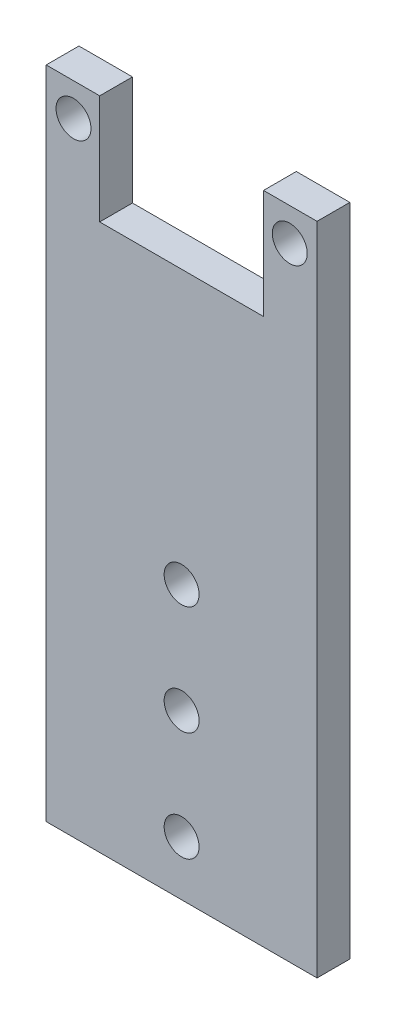
SolidWorks part; units mm, degrees
ref_plane "Front Plane" through (0, 0, 0) normal (0, 0, 1) x (1, 0, 0)
ref_plane "Top Plane" through (0, 0, 0) normal (0, 1, 0) x (1, 0, 0)
ref_plane "Right Plane" through (0, 0, 0) normal (1, 0, 0) x (0, 0, -1)
sketch "Sketch1" plane through (0, 0, 0) normal (0, 0, 1) x (1, 0, 0)
  line L0 (-7.5, 10) -> (-7.5, 0)
  line L1 (-7.5, 0) -> (7.5, 0)
  line L2 (7.5, 0) -> (7.5, 10)
  line L3 (7.5, 10) -> (12.4, 10)
  line L4 (12.4, 10) -> (12.4, -50)
  line L5 (12.4, -50) -> (-12.4, -50)
  line L6 (-12.4, -50) -> (-12.4, 10)
  line L7 (-12.4, 10) -> (-7.5, 10)
  line L8 (-9.9, 7) -> (9.9, 7) construction
  circle A0 centre (-9.9, 7) radius 1.6
  circle A1 centre (9.9, 7) radius 1.6
  circle A2 centre (0, -25) radius 1.6
  circle A3 centre (0, -35) radius 1.6
  circle A4 centre (0, -45) radius 1.6
  point P18 (0, 0)
  point P19 (0, 7)
  point P20 (0, 0)
  point P22 (0, -25)
  dimension "D1" = 3.2
  dimension "D2" = 10
  dimension "D3" = 10
  dimension "D4" = 19.8
  dimension "D5" = 15
  dimension "D6" = 24.8
  dimension "D7" = 7
  dimension "D8" = 10
  dimension "D9" = 50
  dimension "D10" = 25
extrude "Main" add sketch "Sketch1" along normal blind 3
